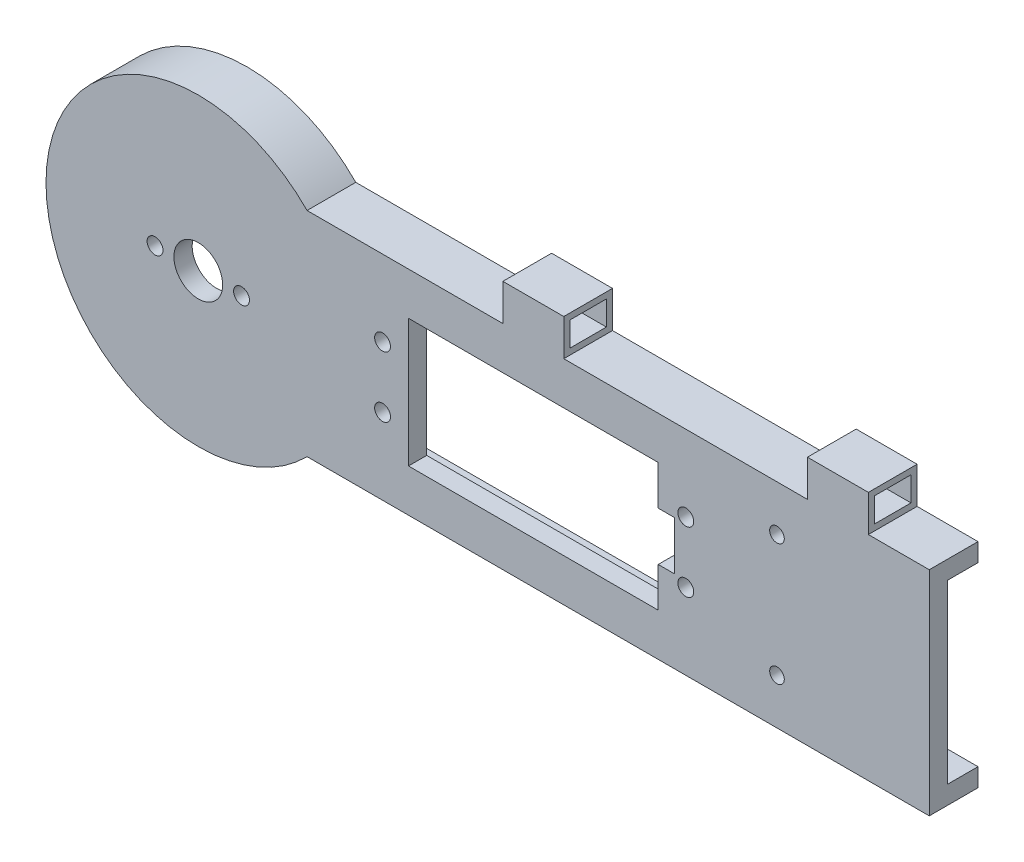
SolidWorks part; units mm, degrees
note: '?' marks a value the reader was unsure of.
material "PLA"
ref_plane "Płaszczyzna przednia" through (0, 0, 0) normal (0, 0, 1) x (1, 0, 0)
ref_plane "Płaszczyzna górna" through (0, 0, 0) normal (0, 1, 0) x (1, 0, 0)
ref_plane "Płaszczyzna prawa" through (0, 0, 0) normal (1, 0, 0) x (0, 0, -1)
sketch "Szkic1" plane through (0, 0, 0) normal (0, 0, 1) x (1, 0, 0)
  line L0 (17.8536, 17.5) -> (182.1464, 17.5)
  line L1 (17.8536, -17.5) -> (182.1464, -17.5)
  arc A0 (17.8536, 17.5) -> (17.8536, -17.5) centre (0, 0) ccw
  arc A1 (182.1464, -17.5) -> (182.1464, 17.5) centre (200, 0) ccw
  dimension "D1" = 50
  dimension "D3" = 50
  dimension "D2" = 200
  dimension "D4" = 35
  dimension "D5" = 17.5
extrude "Dodanie-wyciągnięcie1" add sketch "Szkic1" along normal blind 8
sketch "Szkic2" plane through (0, 0, 8) normal (0, 0, 1) x (1, 0, 0)
  point P0 (-7.1, 0)
  point P1 (7.1, 0)
  dimension "D1" = 14.2
  dimension "D2" = 7.1
hole_wizard "Otwór pod śrubę M22" positions "Szkic11" profile "Szkic12" hole size "M2" standard "ISO" end condition up to next
sketch "Szkic11" plane through (0, 0, 8) normal (0, 0, -1) x (-1, 0, 0)
  arc A0 (-182.1464, 17.5) -> (-182.1464, -17.5) centre (-200, 0) ccw construction
  point P0 (-200, 0)
sketch "Szkic12" plane through (200, 0, 8) normal (1, 0, 0) x (0, -1, 0)
  line L0 (0, 0) -> (0, 8)
  line L1 (0, 8) -> (1.3, 8)
  line L2 (1.3, 8) -> (1.3, 0)
  line L5 (1.3, 0) -> (0, 0)
  line L11 (0, -6.35) -> (0, 107.95) construction
  dimension "Średnica otworu na wylot" = 2.6
  dimension "Głębokość otworu na wylot" = 8
shell "Skorupa1" thickness 3 removed face at (201.3, 0, 0)
sketch "Szkic15" plane through (0, 0, 0) normal (0, 0, -1) x (-1, 0, 0)
  line L0 (-16.5454, -14.5) -> (-183.4546, -14.5) construction
  line L1 (-183.4546, 14.5) -> (-16.5454, 14.5) construction
  line L2 (-16.5454, -14.5) -> (-19.1246, -14.5)
  line L3 (-16.5454, 14.5) -> (-19.1246, 14.5)
  line L4 (-180.8754, -14.5) -> (-183.4546, -14.5)
  line L5 (-180.8754, 14.5) -> (-183.4546, 14.5)
  arc A0 (-16.5454, -14.5) -> (-16.5454, 14.5) centre (0, 0) cw
  arc A1 (-16.5454, -14.5) -> (-16.5454, 14.5) centre (0, 0) ccw construction
  arc A2 (-19.1246, -14.5) -> (-19.1246, 14.5) centre (0, 0) cw
  arc A3 (-183.4546, -14.5) -> (-183.4546, 14.5) centre (-200, 0) ccw
  arc A4 (-183.4546, 14.5) -> (-183.4546, -14.5) centre (-200, 0) ccw construction
  arc A5 (-180.8754, -14.5) -> (-180.8754, 14.5) centre (-200, 0) ccw
  dimension "D1" = 2
  dimension "D2" = 22
  dimension "D3" = 24
  dimension "D4" = 2
extrude "Dodanie-wyciągnięcie2" add sketch "Szkic15" against normal up to next
hole_wizard "Otwór pod śrubę M21" positions "Szkic3" profile "Szkic4" hole size "M2" standard "ISO" end condition up to next
sketch "Szkic3" plane through (0, 0, 8) normal (0, 0, 1) x (1, 0, 0)
  point P0 (7.1, 0)
  point P3 (-7.1, 0)
sketch "Szkic4" plane through (7.1, 0, 8) normal (1, 0, 0) x (0, -1, 0)
  line L0 (0, 0) -> (0, 3)
  line L1 (0, 3) -> (1.3, 3)
  line L2 (1.3, 3) -> (1.3, 0)
  line L5 (1.3, 0) -> (0, 0)
  line L11 (0, -6.35) -> (0, 107.95) construction
  dimension "Średnica otworu na wylot" = 2.6
  dimension "Głębokość otworu na wylot" = 3
sketch "Szkic7" plane through (0, 0, 0) normal (0, 0, -1) x (-1, 0, 0)
  line L1 (-34.5, -10.5) -> (-75.5, -10.5)
  line L2 (-34.5, -10.5) -> (-34.5, 10.5)
  line L3 (-34.5, 10.5) -> (-75.5, 10.5)
  line L4 (-75.5, -10.5) -> (-75.5, 10.5)
  line L5 (-34.5, -10.5) -> (-75.5, 10.5) construction
  line L6 (-34.5, 10.5) -> (-75.5, -10.5) construction
  point P0 (-55, 0)
  dimension "D1" = 21
  dimension "D2" = 41
  dimension "D3" = 55
extrude "Wytnij-wyciągnięcie1" cut sketch "Szkic7" against normal up to next
hole_wizard "Otwory ustalające Ø8.0mm1" positions "Szkic5" profile "Szkic6" hole size "Ø8.0" standard "ISO" end condition up to next
sketch "Szkic5" plane through (0, 0, 8) normal (0, 0, -1) x (-1, 0, 0)
  point P0 (0, 0)
sketch "Szkic6" plane through (0, 0, 8) normal (1, 0, 0) x (0, -1, 0)
  line L0 (0, 0) -> (0, 3)
  line L1 (0, 3) -> (4, 3)
  line L2 (4, 3) -> (4, 0)
  line L5 (4, 0) -> (0, 0)
  line L11 (0, -6.35) -> (0, 107.95) construction
  dimension "Średnica otworu na wylot" = 8
  dimension "Głębokość otworu na wylot" = 3
sketch "Szkic8" plane through (0, 0, 8) normal (0, 0, -1) x (-1, 0, 0)
  line L0 (-29.4366, -0.9508) -> (-31.0634, -9.0492)
  line L1 (-30.25, -5) -> (-80.03, -5)
  line L2 (-30.25, -5) -> (-30.25, 5)
  line L3 (-30.25, 5) -> (-80.03, 5)
  line L4 (-80.03, -5) -> (-80.03, 5)
  line L5 (-30.25, -5) -> (-80.03, 5) construction
  line L6 (-30.25, 5) -> (-80.03, -5) construction
  line L7 (-34.5, -10.5) -> (-34.5, 10.5) construction
  line L8 (-29.3937, 0.7373) -> (-31.1063, 9.2627)
  line L9 (-79.3612, -8.3294) -> (-80.6988, -1.6706)
  line L10 (-79.4671, 7.8023) -> (-80.5929, 2.1977)
  point P0 (-55.14, 0)
  point P11 (-30.25, -5)
  point P14 (-30.25, 5)
  point P17 (-80.03, -5)
  point P20 (-80.03, 5)
  dimension "D1" = 49.78
  dimension "D2" = 10
  dimension "D3" = 10
  dimension "D4" = 4.25
  dimension "D5" = 90
  dimension "D6" = 90
  dimension "D7" = 90
  dimension "D8" = 90
hole_wizard "Otwór pod śrubę M23" positions "Szkic9" profile "Szkic10" hole size "M2" standard "ISO" end condition up to next
sketch "Szkic9" plane through (0, 0, 8) normal (0, 0, -1) x (-1, 0, 0)
  point P0 (-80.03, -5)
  point P3 (-80.03, 5)
  point P6 (-30.25, 5)
  point P9 (-30.25, -5)
sketch "Szkic10" plane through (80.03, -5, 8) normal (1, 0, 0) x (0, -1, 0)
  line L0 (0, 0) -> (0, 3)
  line L1 (0, 3) -> (1.3, 3)
  line L2 (1.3, 3) -> (1.3, 0)
  line L5 (1.3, 0) -> (0, 0)
  line L11 (0, -6.35) -> (0, 107.95) construction
  dimension "Średnica otworu na wylot" = 2.6
  dimension "Głębokość otworu na wylot" = 3
sketch "Szkic13" plane through (0, 0, 0) normal (0, 0, -1) x (-1, 0, 0)
  line L1 (-73, -4) -> (-78.14, -4)
  line L2 (-73, -4) -> (-73, 4)
  line L3 (-73, 4) -> (-78.14, 4)
  line L4 (-78.14, -4) -> (-78.14, 4)
  line L5 (-73, -4) -> (-78.14, 4) construction
  line L6 (-73, 4) -> (-78.14, -4) construction
  line L7 (-75.5, 10.5) -> (-75.5, -10.5) construction
  line L8 (-34.5, 10.5) -> (-75.5, 10.5) construction
  point P0 (-75.57, 0)
  dimension "D1" = 8
  dimension "D2" = 23
  dimension "D3" = 2.5
  dimension "D4" = 6.5
  dimension "D5" = 10.5
extrude "Wytnij-wyciągnięcie2" cut sketch "Szkic13" against normal up to next
ref_plane "Płaszczyzna1" through (0, 0, 0) normal (0, 1, 0) x (1, 0, 0)
sketch "Szkic17" plane through (0, 0, 0) normal (0, 1, 0) x (1, 0, 0)
  point P4 (65.16, -6)
ref_axis "Oś1" through (65.16, 0, 6) along (0, 0, 1)?
ref_plane "Płaszczyzna2" through (50, 0, 0) normal (1, 0, 0) x (0, 0, -1)
sketch "Szkic18" plane through (50, 0, 0) normal (1, 0, 0) x (0, 0, -1)
  line L0 (0, -22) -> (0, 22) construction
  line L1 (-8, 23.5) -> (0, 23.5)
  line L2 (-8, 23.5) -> (-8, 17.5)
  line L3 (-8, 17.5) -> (0, 17.5)
  line L4 (0, 23.5) -> (0, 17.5)
  line L5 (-8, 23.5) -> (0, 17.5) construction
  line L6 (-8, 17.5) -> (0, 23.5) construction
  line L7 (-8, 25) -> (-8, -25) construction
  line L8 (-8, 17.5) -> (0, 17.5) construction
  line L9 (-7, 22.5) -> (-1, 22.5)
  line L10 (-1, 22.5) -> (-1, 18.5)
  line L11 (-7, 18.5) -> (-1, 18.5)
  line L12 (-7, 22.5) -> (-7, 18.5)
  point P0 (-4, 20.5)
  dimension "D1" = 6
  dimension "D2" = 1
extrude "Dodanie-wyciągnięcie3" add sketch "Szkic18" along normal blind 10
pattern_linear "Szyk liniowy1" count 2 spacing 50 along (1, 0, 0) of "Dodanie-wyciągnięcie3"
sketch "Szkic19" plane through (0, 0, 5) normal (0, 0, -1) x (-1, 0, 0)
  line L1 (-95, -10) -> (-145, -10)
  line L2 (-95, -10) -> (-95, 10)
  line L3 (-95, 10) -> (-145, 10)
  line L4 (-145, -10) -> (-145, 10)
  line L5 (-95, -10) -> (-145, 10) construction
  line L6 (-95, 10) -> (-145, -10) construction
  line L11 (-100, 17.5) -> (-60, 17.5) construction
  circle A0 centre (0, 0) radius 4 construction
  point P0 (-120, 0)
  dimension "D1" = 17.5
  dimension "25" = 50
  dimension "D2" = 20
  dimension "D3" = 120
  dimension "D4" = 17.5
  dimension "D5" = 2.2
ref_plane "Płaszczyzna3" through (120, 0, 0) normal (1, 0, 0) x (0, 0, -1)
hole_wizard "Otwór pod śrubę M24" positions "Szkic22" profile "Szkic21" hole size "M2" standard "ISO" end condition through all
sketch "Szkic22" plane through (0, 0, 5) normal (0, 0, -1) x (-1, 0, 0)
  point P0 (-145, -10)
  point P3 (-145, 10)
  point P6 (-95, 10)
  point P9 (-95, -10)
  dimension "D1" = 20
sketch "Szkic21" plane through (145, -10, 5) normal (1, 0, 0) x (0, 1, 0)
  line L0 (0, 0) -> (0, 3)
  line L1 (0, 3) -> (1.2, 3)
  line L2 (1.2, 3) -> (1.2, 0)
  line L5 (1.2, 0) -> (0, 0)
  line L11 (0, -6.35) -> (0, 107.95) construction
  dimension " rednica otworu na wylot" = 2.4
  dimension "G³êboko æ otworu na wylot" = 3
other "Cięcie powierzchnią1" flip cut yes
ref_plane "Blat stołu" through (0, 0, 8) normal (0, 0, 1) x (1, 0, 0)
